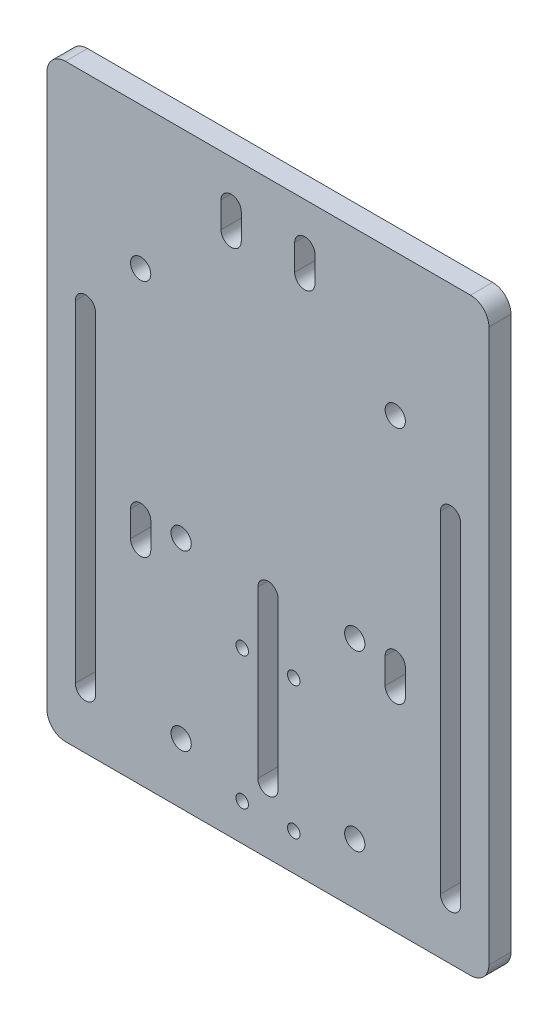
SolidWorks part; units mm, degrees
ref_plane "Front Plane" through (0, 0, 0) normal (0, 0, 1) x (1, 0, 0)
ref_plane "Top Plane" through (0, 0, 0) normal (0, 1, 0) x (1, 0, 0)
ref_plane "Right Plane" through (0, 0, 0) normal (1, 0, 0) x (0, 0, -1)
sketch "Sketch2" plane through (0, 0, 0) normal (0, 0, 1) x (1, 0, 0)
  line L1 (-55, -80) -> (55, -80)
  line L2 (-60, -75) -> (-60, 75)
  line L3 (-55, 80) -> (55, 80)
  line L4 (60, -75) -> (60, 75)
  line L5 (-60, -80) -> (60, 80) construction
  line L6 (-60, 80) -> (60, -80) construction
  arc A0 (55, -80) -> (60, -75) centre (55, -75) ccw
  arc A1 (-55, -80) -> (-60, -75) centre (-55, -75) cw
  arc A2 (55, 80) -> (60, 75) centre (55, 75) cw
  arc A3 (-60, 75) -> (-55, 80) centre (-55, 75) cw
  point P0 (0, 0)
  dimension "D3" = 5
  dimension "D1" = 120
  dimension "D2" = 160
extrude "Boss-Extrude1" add sketch "Sketch2" along normal blind 6
sketch "Sketch3" plane through (0, 0, 6) normal (0, 0, 1) x (1, 0, 0)
  line L0 (0, -17.5) -> (0, -62.5) construction
  line L1 (2.75, -17.5) -> (2.75, -62.5)
  line L2 (-2.75, -17.5) -> (-2.75, -62.5)
  line L3 (-55, -80) -> (55, -80) construction
  arc A0 (2.75, -17.5) -> (-2.75, -17.5) centre (0, -17.5) ccw
  arc A1 (-2.75, -62.5) -> (2.75, -62.5) centre (0, -62.5) ccw
  point P3 (0, -40)
  dimension "D1" = 2.75
  dimension "D2" = 45
  dimension "D3" = 40
extrude "Cut-Extrude1" cut sketch "Sketch3" against normal blind 6
hole_wizard "M5 Clearance Hole1" positions "Sketch4" profile "Sketch5" hole size "M5" standard "ANSI Metric" end condition through all
sketch "Sketch4" plane through (0, 0, 6) normal (0, 0, 1) x (1, 0, 0)
  point P0 (-23.57, -63.57)
  point P2 (-23.57, -16.43)
  point P4 (23.57, -16.43)
  point P6 (23.57, -63.57)
  dimension "D1" = 23.57
  dimension "D2" = 23.57
  dimension "D3" = 23.57
  dimension "D4" = 47.14
sketch "Sketch5" plane through (-23.57, -63.57, 6) normal (1, 0, 0) x (0, -1, 0)
  line L0 (0, 0) -> (0, 6)
  line L1 (0, 6) -> (2.75, 6)
  line L2 (2.75, 6) -> (2.75, 0)
  line L5 (2.75, 0) -> (0, 0)
  line L11 (0, -6.35) -> (0, 107.95) construction
  dimension "Thru Hole Dia." = 5.5
  dimension "Thru Hole Depth" = 6
sketch "Sketch6" plane through (0, 0, 6) normal (0, 0, 1) x (1, 0, 0)
  line L0 (-34.57, -16.43) -> (-34.57, -23.43) construction
  line L1 (-31.82, -16.43) -> (-31.82, -23.43)
  line L2 (-37.32, -16.43) -> (-37.32, -23.43)
  arc A0 (-31.82, -16.43) -> (-37.32, -16.43) centre (-34.57, -16.43) ccw
  arc A1 (-37.32, -23.43) -> (-31.82, -23.43) centre (-34.57, -23.43) ccw
  point P2 (-34.57, -19.93)
  dimension "D1" = 2.75
  dimension "D2" = 7
  dimension "D3" = 11
extrude "Cut-Extrude2" cut sketch "Sketch6" against normal blind 22
hole_wizard "M5 Clearance Hole2" positions "Sketch7" profile "Sketch8" hole size "M5" standard "ANSI Metric" end condition through all
sketch "Sketch7" plane through (0, 0, 6) normal (0, 0, 1) x (1, 0, 0)
  point P0 (-34.57, 41.47)
  dimension "D1" = 61.4
sketch "Sketch8" plane through (-34.57, 41.47, 6) normal (1, 0, 0) x (0, -1, 0)
  line L0 (0, 0) -> (0, 6)
  line L1 (0, 6) -> (2.75, 6)
  line L2 (2.75, 6) -> (2.75, 0)
  line L5 (2.75, 0) -> (0, 0)
  line L11 (0, -6.35) -> (0, 107.95) construction
  dimension "Thru Hole Dia." = 5.5
  dimension "Thru Hole Depth" = 6
sketch "Sketch9" plane through (0, 0, 6) normal (0, 0, 1) x (1, 0, 0)
  line L0 (-49.57, 25.07) -> (-49.57, -64.93) construction
  line L1 (-46.82, 25.07) -> (-46.82, -64.93)
  line L2 (-52.32, 25.07) -> (-52.32, -64.93)
  arc A0 (-46.82, 25.07) -> (-52.32, 25.07) centre (-49.57, 25.07) ccw
  arc A1 (-52.32, -64.93) -> (-46.82, -64.93) centre (-49.57, -64.93) ccw
  point P2 (-49.57, -19.93)
  dimension "D2" = 2.75
  dimension "D1" = 15
  dimension "D3" = 90
extrude "Cut-Extrude3" cut sketch "Sketch9" against normal blind 6
sketch "Sketch10" plane through (0, 0, 6) normal (0, 0, 1) x (1, 0, 0)
  line L0 (0, 85.855) -> (0, -97.3195) construction
mirror "Mirror2" about plane through (0, 0, 0) normal (1, 0, 0) of "M5 Clearance Hole2", "Cut-Extrude3", "Cut-Extrude2"
sketch "Sketch11" plane through (0, 0, 6) normal (0, 0, 1) x (1, 0, 0)
  line L0 (-10, 68.5) -> (-10, 61.5) construction
  line L1 (-7.25, 68.5) -> (-7.25, 61.5)
  line L2 (-12.75, 68.5) -> (-12.75, 61.5)
  line L3 (10, 68.5) -> (10, 61.5) construction
  line L4 (12.75, 68.5) -> (12.75, 61.5)
  line L5 (7.25, 68.5) -> (7.25, 61.5)
  line L9 (55, 80) -> (-55, 80) construction
  arc A0 (-7.25, 68.5) -> (-12.75, 68.5) centre (-10, 68.5) ccw
  arc A1 (-12.75, 61.5) -> (-7.25, 61.5) centre (-10, 61.5) ccw
  arc A2 (12.75, 68.5) -> (7.25, 68.5) centre (10, 68.5) ccw
  arc A3 (7.25, 61.5) -> (12.75, 61.5) centre (10, 61.5) ccw
  point P2 (-10, 65)
  point P7 (10, 65)
  dimension "D1" = 2.75
  dimension "D4" = 10
  dimension "D2" = 7
  dimension "D3" = 20
  dimension "D5" = 15
extrude "Cut-Extrude4" cut sketch "Sketch11" against normal blind 6
hole_wizard "M3 Clearance Hole1" positions "Sketch12" profile "Sketch13" hole size "M3" standard "ANSI Metric"
sketch "Sketch12" plane through (0, 0, 6) normal (0, 0, 1) x (1, 0, 0)
  line L0 (0, 85.855) -> (0, -97.3195) construction
  line L1 (-55, -80) -> (55, -80) construction
  point P0 (-7, -34)
  point P2 (7, -34)
  point P4 (7, -70)
  point P6 (-7, -70)
  dimension "D1" = 7
  dimension "D2" = 14
  dimension "D3" = 36
  dimension "D4" = 10
sketch "Sketch13" plane through (-7, -34, 6) normal (1, 0, 0) x (0, -1, 0)
  line L0 (0, 0) -> (0, 11.0215)
  line L1 (0, 11.0215) -> (1.7, 10)
  line L2 (1.7, 10) -> (1.7, 0)
  line L5 (1.7, 0) -> (0, 0)
  line L10 (0, 11.0215) -> (-1.7, 10) construction
  line L11 (0, -6.35) -> (0, 107.95) construction
  dimension "Hole Dia." = 3.4
  dimension "Hole Depth" = 10
  dimension "Drill Angle" = 118
